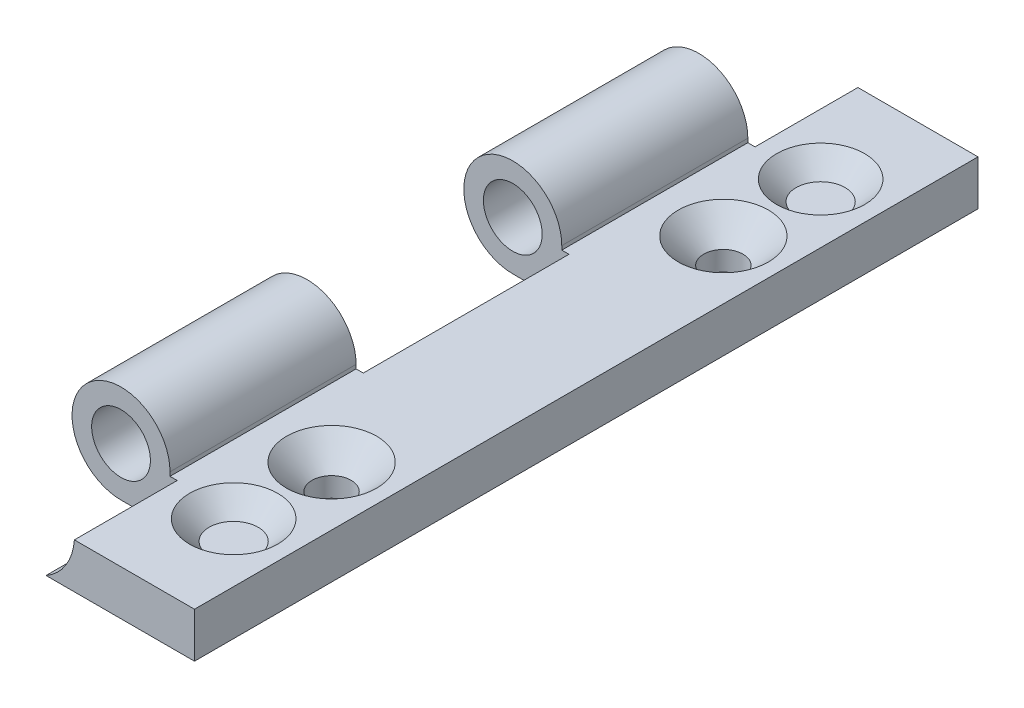
SolidWorks part; units mm, degrees
ref_plane "Front Plane" through (0, 0, 0) normal (0, 0, 1) x (1, 0, 0)
ref_plane "Top Plane" through (0, 0, 0) normal (0, 1, 0) x (1, 0, 0)
ref_plane "Right Plane" through (0, 0, 0) normal (1, 0, 0) x (0, 0, -1)
sketch "Sketch1" plane through (0, 0, 0) normal (0, 1, 0) x (1, 0, 0)
  line L1 (0, 0) -> (-9, 0)
  line L2 (0, 0) -> (0, 40)
  line L3 (0, 40) -> (-9, 40)
  line L4 (-9, 0) -> (-9, 40)
  dimension "D1" = 40
  dimension "D2" = 9
extrude "Boss-Extrude1" add sketch "Sketch1" along normal blind 2.5
sketch "Sketch2" plane through (0, 0, 0) normal (0, 0, 1) x (1, 0, 0)
  circle A0 centre (-9, 2.5) radius 2.5
extrude "Boss-Extrude2" add sketch "Sketch2" against normal blind 9.5 from offset 5.25 offset against normal yes
ref_plane "Plane1" through (0, 0, -20) normal (0, 0, 1) x (1, 0, 0)
sketch "Sketch3" plane through (0, 0, 0) normal (0, 0, 1) x (1, 0, 0)
  circle A0 centre (-9, 2.5) radius 1.5
  dimension "D1" = 3
extrude "Cut-Extrude1" cut sketch "Sketch3" against normal through all
sketch "Sketch4" plane through (0, 0, 0) normal (0, 0, 1) x (1, 0, 0)
  circle A0 centre (-9, 2.5) radius 2.875
  dimension "D1" = 5.75
extrude "Cut-Extrude2" cut sketch "Sketch4" against normal up to surface (5.25 mm away) up to face at (-9.2071, 2.7071, -5.25)
extrude "Cut-Extrude3" cut sketch "Sketch4<2>" along normal up to surface (-14.75 mm away) from surface up to face at (-9.2071, 2.7071, -14.75) starting at plane "Plane1"
sketch "Sketch4<2>" plane through (0, 0, 0) normal (0, 0, 1) x (1, 0, 0) same geometry as "Sketch4"
mirror "Mirror2" about plane through (0, 0, -20) normal (0, 0, 1) of "Cut-Extrude3", "Cut-Extrude2", "Cut-Extrude1", "Boss-Extrude2"
sketch "Sketch5" plane through (0, 2.5, 0) normal (0, 1, 0) x (1, 0, 0)
  line L0 (0, 0) -> (0, 40) construction
  line L1 (-6.125, 0) -> (0, 0) construction
  circle A0 centre (-3, 10) radius 1
  dimension "D1" = 2
  dimension "D2" = 3
  dimension "D3" = 10
extrude "Cut-Extrude4" cut sketch "Sketch5" against normal through all
mirror "Mirror3" about plane through (0, 0, -20) normal (0, 0, 1) of "Cut-Extrude4"
chamfer "Chamfer1" distance 1.5 angle 45 1 edges at (-3, 2.5, -31)
chamfer "Chamfer2" distance 1.5 angle 45 1 edges at (-3, 2.5, -9)
sketch "Sketch7" plane through (0, 0, 0) normal (0, 0, 1) x (1, 0, 0)
  line L0 (0, 2.5) -> (0, 0) construction
  line L1 (-6.5, 2.5) -> (0, 2.5)
  line L2 (-6.5, 2.5) -> (-6.5, 2.3)
  line L3 (-6.5, 2.3) -> (0, 2.3)
  line L4 (0, 2.5) -> (0, 2.3)
  dimension "D1" = 0.2
extrude "Cut-Extrude5" cut sketch "Sketch7" against normal through all
sketch "Sketch8" plane through (0, 2.3, 0) normal (0, 1, 0) x (1, 0, 0)
  line L0 (-3, 35) -> (0, 35) construction
  line L1 (0, 40) -> (0, 0) construction
  line L2 (-3, 5) -> (0, 5) construction
  line L3 (-3, 30) -> (-3.066, 40) construction
  line L4 (-6.132, 40) -> (0, 40) construction
  line L5 (-3, 10) -> (-3, 1.2632) construction
  circle A0 centre (-3.033, 35) radius 1.25
  circle A1 centre (-3, 5) radius 1.25
  dimension "D1" = 2.5
  dimension "D2" = 2.5
extrude "Cut-Extrude6" cut sketch "Sketch8" against normal blind 1
chamfer "Chamfer3" distance 1 angle 45 2 edges at (-3, 2.3, -3.75) (-3.033, 2.3, -33.75)
